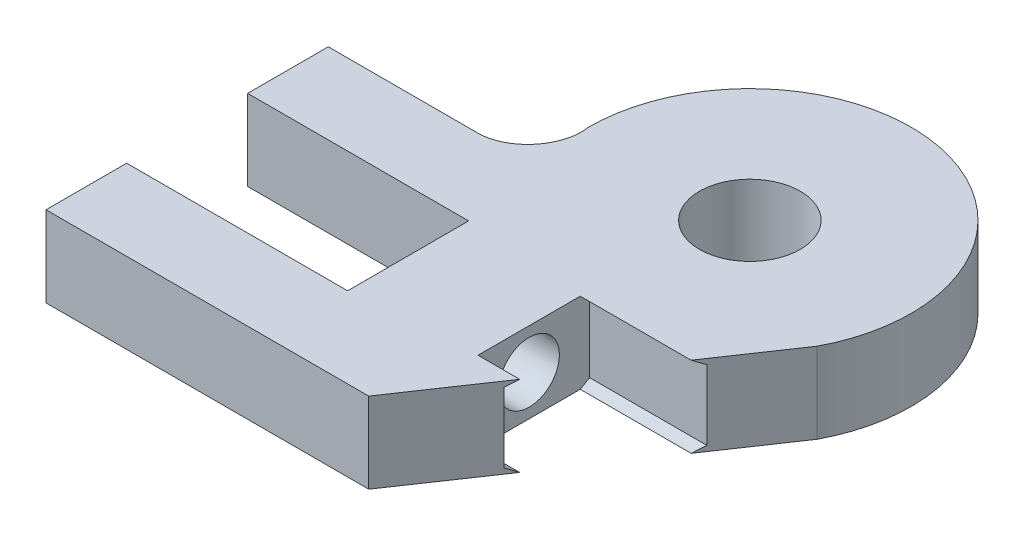
SolidWorks part; units mm, degrees
note: The reader was unsure of these and kept them because the rebuilt part matched: shared geometry of "Sketch2<3>".
ref_plane "Plan de face" through (0, 0, 0) normal (0, 0, 1) x (1, 0, 0)
ref_plane "Plan de dessus" through (0, 0, 0) normal (0, 1, 0) x (1, 0, 0)
ref_plane "Plan de droite" through (0, 0, 0) normal (1, 0, 0) x (0, 0, -1)
sketch "Sketch1" plane through (0, 0, 0) normal (0, 1, 0) x (1, 0, 0)
  line L0 (-11.3405, 5.6088) -> (-11.3405, 1.6088)
  line L1 (-11.3405, 1.6088) -> (-0.3817, 1.6088)
  line L2 (-0.3817, 1.6088) -> (-0.3817, -4.3912)
  line L3 (-0.3817, -4.3912) -> (-11.3405, -4.3912)
  line L4 (-11.3405, -4.3912) -> (-11.3405, -8.3912)
  line L5 (-11.3405, -8.3912) -> (4.6646, -8.3912)
  line L6 (-11.3405, 5.6088) -> (-3.9172, 5.6088)
  line L7 (4.6646, -8.3912) -> (13.6386, 4.8702)
  circle A0 centre (6.5659, 8.6088) radius 2.5
  circle A1 centre (6.5659, 8.6088) radius 8
  spline S1 degree 3 poles (-3.9172, 5.6088) (-2.4076, 5.6272) (-1.1984, 7.123) (-1.4341, 8.6088) knots 0 0 0 0 1 1 1 1
  point P31 (-0.3817, -1.3912)
  dimension "D1" = 5
  dimension "D2" = 16
  dimension "D3" = 4
  dimension "D4" = 4
  dimension "D5" = 6
  dimension "D6" = 10
extrude "Boss-Extrude1" add sketch "Sketch1" along normal blind 4
sketch "Sketch2" plane through (-0.3817, 0, 0) normal (-1, 0, 0) x (0, 0, 1)
  line L1 (-1.6088, 0.2679) -> (1.3912, -1.4641)
  line L2 (1.3912, -1.4641) -> (4.3912, 0.2679)
  line L3 (4.3912, 0.2679) -> (4.3912, 3.7321)
  line L4 (4.3912, 3.7321) -> (1.3912, 5.4641)
  line L5 (1.3912, 5.4641) -> (-1.6088, 3.7321)
  line L6 (-1.6088, 3.7321) -> (-1.6088, 0.2679)
  line L7 (-1.6088, 4) -> (-1.6088, 0) construction
  line L9 (-1.6088, 2) -> (4.3912, 2) construction
  line L10 (-1.6088, 4) -> (-1.6088, 0) construction
  line L11 (4.3912, 4) -> (4.3912, 0) construction
  circle A0 centre (1.3912, 2) radius 1.5
  circle A1 centre (1.3912, 2) radius 3 construction
  dimension "D1" = 3
  dimension "D2" = 6
extrude "Cut-Extrude1" cut sketch "Sketch2" against normal through all both and the other way through all contours A0
extrude "Cut-Extrude2" cut sketch "Sketch2<3>" against normal through all from offset 6 contours A0 | A0 L3 L4 | A0 L4 L5 | A0 L6 L1 | A0 L1 L2 | A0 L2 L3 | A0 L5 L6
sketch "Sketch2<3>" plane through (-0.3817, 0, 0) normal (-1, 0, 0) x (0, 0, 1) same geometry as "Sketch2"
